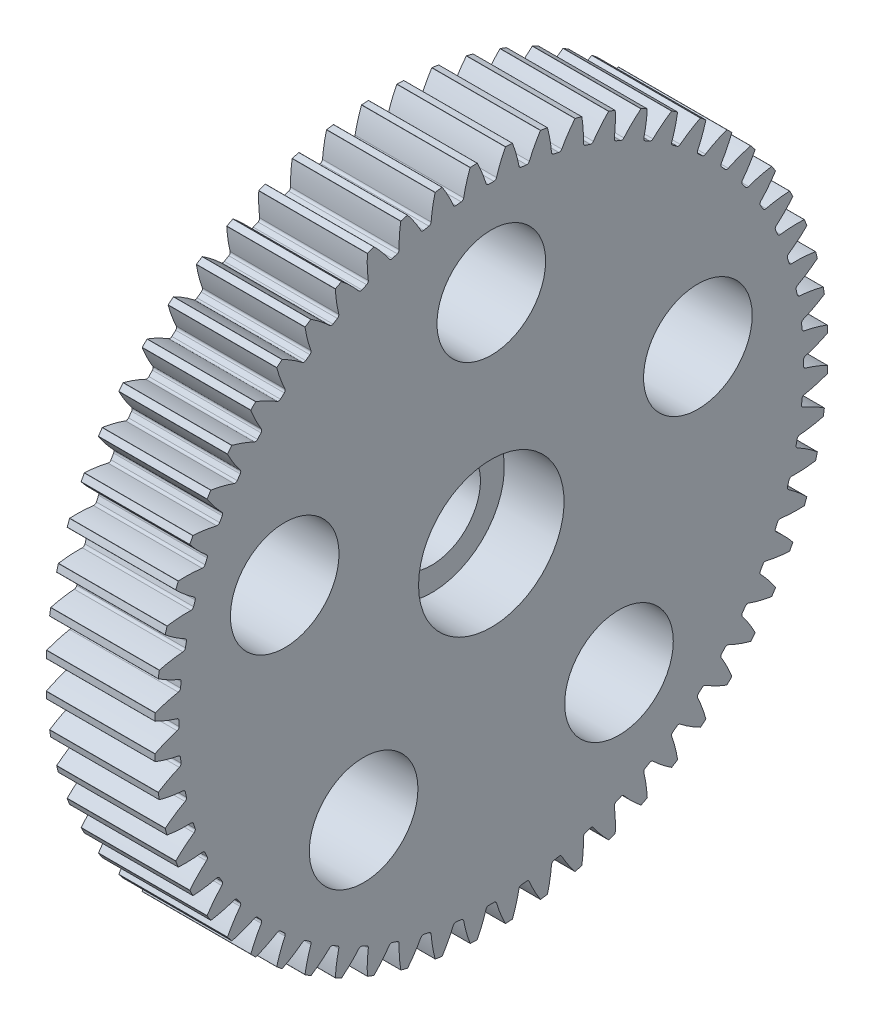
SolidWorks part; units mm, degrees
ref_plane "Plane1" through (0, 0, 0) normal (0, 0, 1) x (1, 0, 0)
ref_plane "Plane2" through (0, 0, 0) normal (0, 1, 0) x (1, 0, 0)
ref_plane "Plane3" through (0, 0, 0) normal (1, 0, 0) x (0, 0, -1)
sketch "HoldingSke" plane through (0, 0, 0) normal (0, 1, 0) x (1, 0, 0)
  line L0 (0, 0) -> (0.5, -0.866)
  line L1 (-15, 0) -> (100, 0) construction
  line L2 (0, 0) -> (-2.1039, 2.3779)
  line L3 (0, 0) -> (-11.863, 4.5341)
  line L4 (0, 0) -> (4.318, 7.479)
  line L5 (0, 0) -> (-46.8476, -17.4728)
  line L6 (0, 0) -> (-4.1448, -2.7965)
  line L7 (-2.1039, 2.3779) -> (8.6586, 51.2061)
  line L8 (-76.2, 54.61) -> (-75.7, 54.61)
  line L9 (-71.009, 38.7566) -> (-53.1078, 45.2721)
  line L10 (-76.2, 71.12) -> (104.1128, 71.12)
  line L11 (0, 0) -> (-5, 0)
  line L12 (-76.2, 101.6) -> (-76.162, 101.6)
  line L13 (24.9733, 27.94) -> (52.9518, 28.4284)
  line L14 (24.9733, 27.94) -> (24.9743, 27.94)
  line L15 (24.9733, 27.94) -> (100.4006, 29.5858)
  line L16 (-63.627, -1) -> (-12.827, -1)
  circle A0 centre (0, 0) radius 1.5
  circle A1 centre (0, 0) radius 28.749
  circle A2 centre (0, 0) radius 37.5
  circle A3 centre (0, 0) radius 1.5
  dimension "Num_teeth" = 60
  dimension "Pitch_radius" = 180.3128
  dimension "Width" = 5
sketch "BasProSke" plane through (0, 0, 0) normal (0, 1, 0) x (1, 0, 0)
  line L0 (-10, 0) -> (60, 0) construction
  line L1 (0, 0) -> (0, 31)
  line L2 (0, 0) -> (10, 0)
  line L3 (10, 0) -> (10, 31)
  line L4 (10, 31) -> (0, 31)
  dimension "Diameter" = 62
  dimension "Thickness" = 10
revolve "Base-Revolve" add sketch "BasProSke" angle 360 about L0
sketch "TooCutSke" plane through (0, 0, 0) normal (1, 0, 0) x (0, 0, -1)
  line L1 (0, 0) -> (0, 107) construction
  line L2 (0, 0) -> (-0.8516, 29.9879) construction
  line L3 (0, 0) -> (-3.1393, 59.9006) construction
  line L4 (-0.8516, 29.9879) -> (-1.5696, 29.9503) construction
  arc A0 (0.43, 28.7458) -> (-0.43, 28.7458) centre (0, 0) ccw
  arc A1 (1.3125, 30.9977) -> (-1.3125, 30.9977) centre (0, 0) ccw
  circle A2 centre (0, 0) radius 30 construction
  circle A3 centre (0, 0) radius 28.191 construction
  arc A4 (-0.43, 28.7458) -> (-1.3125, 30.9977) centre (-11.9871, 25.5155) ccw
  arc A5 (1.3125, 30.9977) -> (0.43, 28.7458) centre (11.9871, 25.5155) ccw
  dimension "Root_dia" = 57.498
  dimension "Overcut_dia" = 62.051
  dimension "Pitch_dia" = 60
  dimension "Base_dia" = 56.382
  dimension "Flank_rad" = 12
  dimension "Half_ang" = 3
  dimension "Half_CT" = 0.719
extrude "ToothCut" cut sketch "TooCutSke" along normal through all
fillet "Breaks" radius 0.02 2 edges at (5, 30.9727, -1.2997) (5, 30.9727, 1.2997) tangent propagation no
fillet "RootFillets" radius 0.251 2 edges at (5, 28.7458, -0.43) (5, 28.7458, 0.43)
pattern_circular "TeethCuts" count 60 every 6 about axis through (-10, 0, 0) along (1, 0, 0) of "ToothCut", "RootFillets", "Breaks"
sketch "BorSke" plane through (0, 0, 0) normal (1, 0, 0) x (0, 0, -1)
  circle A0 centre (0, 0) radius 6.7
  dimension "Diameter" = 13.4
extrude "Bore" cut sketch "BorSke" along normal mid plane 100
sketch "草图2" plane through (0, 0, 0) normal (1, 0, 0) x (0, 0, -1)
  circle A0 centre (0, 20) radius 5
  circle A2 centre (19.0211, 6.1803) radius 5
  circle A3 centre (11.7557, -16.1803) radius 5
  circle A4 centre (-11.7557, -16.1803) radius 5
  circle A5 centre (-19.0211, 6.1803) radius 5
  point P14 (0, 0)
  dimension "D2" = 10
  dimension "D1" = 20
  dimension "D3" = 5
extrude "切除-拉伸2" cut sketch "草图2" along normal blind 10
sketch "草图4" plane through (0, 0, 0) normal (-1, 0, 0) x (0, 0, 1)
  circle A0 centre (0, 0) radius 6.7
  circle A1 centre (0, 0) radius 4.5
  dimension "D1" = 9
extrude "凸台-拉伸1" add sketch "草图4" against normal blind 4.5
equation "' \"Module@HoldingSke\" = 6.35"
equation "' \"Num_teeth@HoldingSke\" = 12"
equation "' \"Ap@HoldingSke\" =  20"
equation "' \"Ap@HoldingSke\" = 20"
equation "' \"Width@HoldingSke\" = 0.5 * 25.4"
equation "' \"Hub_dia@HoldingSke\"= 1 * 25.4"
equation "' \"Hub_dia@HoldingSke\" = 1 * 25.4"
equation "' \"Overall_len@HoldingSke\" = 1.0 * 25.4"
equation "' \"Bore@HoldingSke\" = 0.75 * 25.4"
equation "' \"T_dim@HoldingSke\" = 0.1 * 25.4"
equation "' \"Width@KeySke\" = 0.25 * 25.4"
equation "' \"Show_teeth@HoldingSke\" = 13"
equation "' \"Backlash@HoldingSke\" = 0.009 * 25.4"
equation "' \"Addendum_fac@HoldingSke\" = 1.0"
equation "' \"Dedendum_fac@HoldingSke\" = 1.25"
equation "' \"Dedendum_add@HoldingSke\" = 0.00005 * 25.4"
equation "' \"Clearance_fac@HoldingSke\" = 0.25"
equation "\"Pitch@HoldingSke\" = 1 / \"Module@HoldingSke\""
equation "\"Thickness@HoldingSke\" = \"Width@HoldingSke\""
equation "' \"Fillet_rad@BasProSke\" =  \"Thickness@HoldingSke\" * 0.05"
equation "' \"Fillet_rad@BasProSke\" = \"Thickness@HoldingSke\" * 0.05"
